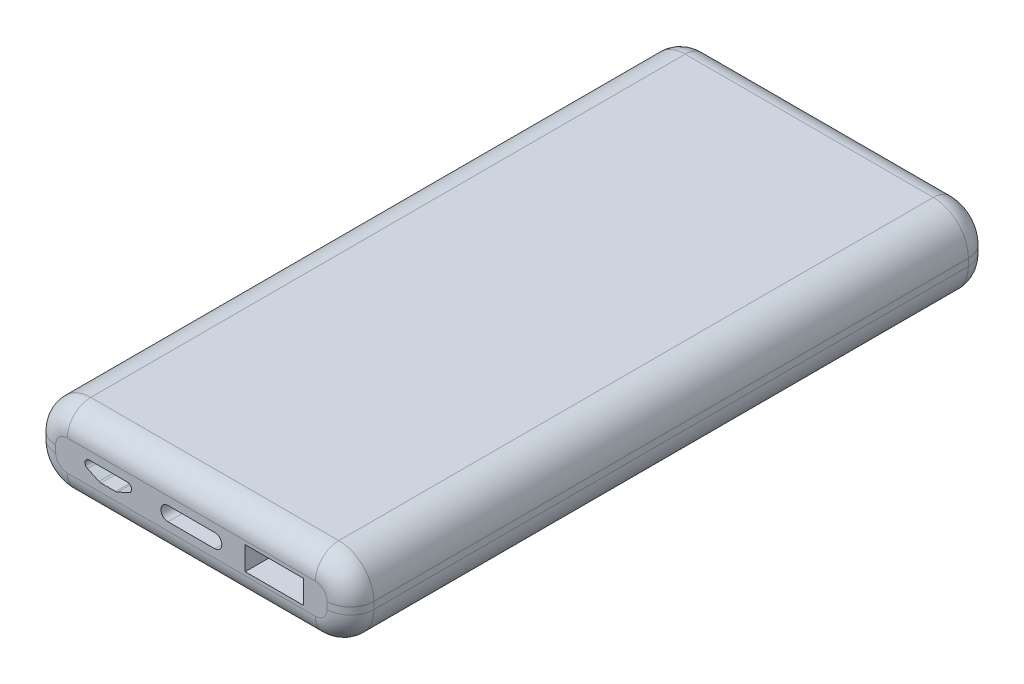
SolidWorks part; units mm, degrees
ref_plane "Plan de face" through (0, 0, 0) normal (0, 0, 1) x (1, 0, 0)
ref_plane "Plan de dessus" through (0, 0, 0) normal (0, 1, 0) x (1, 0, 0)
ref_plane "Plan de droite" through (0, 0, 0) normal (1, 0, 0) x (0, 0, -1)
sketch "Esquisse1" plane through (0, 0, 0) normal (0, 0, 1) x (1, 0, 0)
  line L1 (-34, 8.25) -> (34, 8.25)
  line L2 (-34, 8.25) -> (-34, -8.25)
  line L3 (-34, -8.25) -> (34, -8.25)
  line L4 (34, 8.25) -> (34, -8.25)
  point P4 (0, 8.25)
  point P6 (-34, 0)
  dimension "D1" = 16.5
  dimension "D2" = 68
extrude "Boss.-Extru.1" add sketch "Esquisse1" along normal blind 137
fillet "Congé1" radius 7.5 4 edges at (34, -8.25, 68.5) (34, 8.25, 68.5) (-34, -8.25, 68.5) (-34, 8.25, 68.5)
fillet "Congé2" radius 5 16 edges at (-31.8033, 6.0533, 0) (0, 8.25, 0) (31.8033, 6.0533, 0) (34, 0, 0) (31.8033, -6.0533, 0) (0, -8.25, 0) (-31.8033, -6.0533, 0) (-31.8033, 6.0533, 137) (0, 8.25, 137) (31.8033, 6.0533, 137) (34, 0, 137) (31.8033, -6.0533, 137) (0, -8.25, 137) (-31.8033, -6.0533, 137) (-34, 0, 0) (-34, 0, 137)
sketch "Esquisse2" plane through (0, 0, 137) normal (0, 0, 1) x (1, 0, 0)
  line L0 (5, 0) -> (-5, 0) construction
  line L1 (-22.75, 1.5) -> (-12.75, 1.5)
  line L2 (-22.75, 1.5) -> (-22.75, -1.5)
  line L3 (-22.75, -1.5) -> (-12.75, -1.5) construction
  line L4 (-12.75, 1.5) -> (-12.75, -1.5)
  line L5 (11.5, 2.5) -> (24, 2.5)
  line L6 (11.5, 2.5) -> (11.5, -2.5)
  line L7 (11.5, -2.5) -> (24, -2.5)
  line L8 (24, 2.5) -> (24, -2.5)
  line L13 (5, -1.5) -> (-5, -1.5)
  line L14 (5, 1.5) -> (-5, 1.5)
  line L15 (11.5, 0) -> (6.5, 0) construction
  line L16 (24, 0) -> (29, 0) construction
  line L17 (29, -0.75) -> (29, 0.75) construction
  line L18 (-12.75, 0) -> (-6.5, 0) construction
  line L19 (-22.75, 0) -> (-29, 0) construction
  line L20 (-29, 0.75) -> (-29, -0.75) construction
  line L21 (-22.75, 0) -> (-19.5273, -1.5)
  line L22 (-19.5273, -1.5) -> (-15.9727, -1.5)
  line L23 (-15.9727, -1.5) -> (-12.75, 0)
  arc A0 (5, -1.5) -> (5, 1.5) centre (5, 0) ccw
  arc A1 (-5, 1.5) -> (-5, -1.5) centre (-5, 0) ccw
  point P10 (0, 0)
  point P15 (-12.75, 0)
  point P16 (11.5, 0)
  dimension "D4" = 10
  dimension "D1" = 12.5
  dimension "D2" = 5
  dimension "D3" = 3
extrude "Enlèv. mat.-Extru.1" cut sketch "Esquisse2" against normal blind 5 contours L22 L23 L4 L1 L2 L21 | L14 A1 L13 A0 | L8 L5 L6 L7 region at (-17.75, 0.1921, 137) region at (17.75, 0, 137) region at (0, 0, 137)
fillet "Congé3" radius 1 6 edges at (-15.9727, -1.5, 134.5) (-19.5273, -1.5, 134.5) (-22.75, 0, 134.5) (-22.75, 1.5, 134.5) (-12.75, 1.5, 134.5) (-12.75, 0, 134.5)
